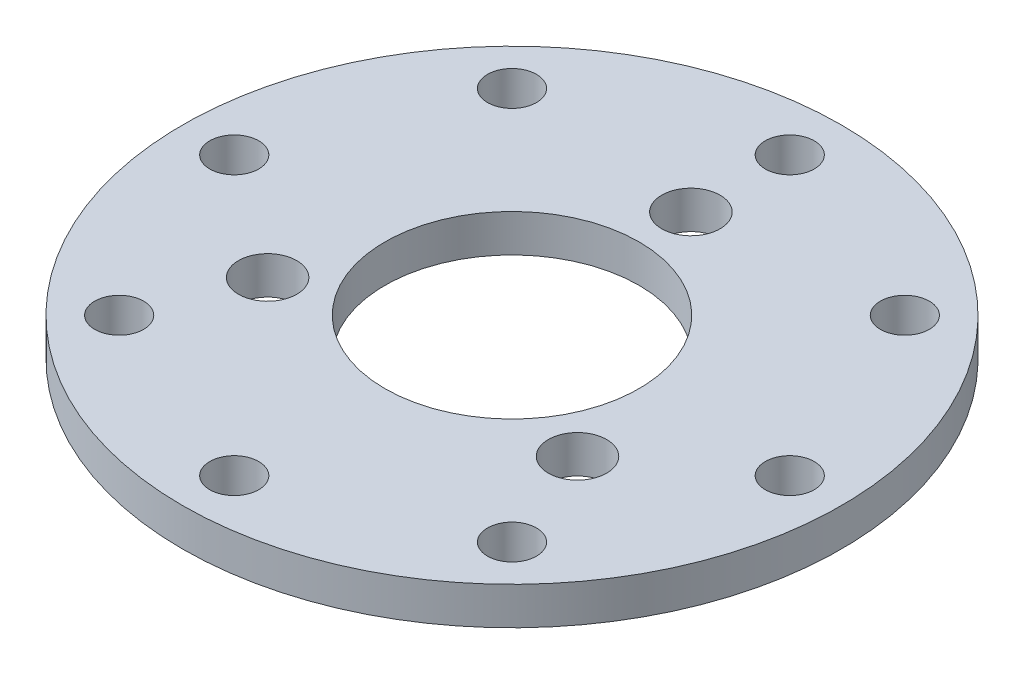
SolidWorks part; units mm, degrees
ref_plane "前视基准面" through (0, 0, 0) normal (0, 0, 1) x (1, 0, 0)
ref_plane "上视基准面" through (0, 0, 0) normal (0, 1, 0) x (1, 0, 0)
ref_plane "右视基准面" through (0, 0, 0) normal (1, 0, 0) x (0, 0, -1)
sketch "草图1" plane through (0, 0, 0) normal (0, 1, 0) x (1, 0, 0)
  line L0 (0, 0) -> (0, 9.5) construction
  line L1 (0, 0) -> (0, 9.5) construction
  circle A0 centre (0, 0) radius 17.5
  circle A1 centre (0, 0) radius 6.75
  circle A2 centre (0, 9.5) radius 1.55
  circle A3 centre (8.2272, -4.75) radius 1.55
  circle A4 centre (-8.2272, -4.75) radius 1.55
  dimension "D1" = 35
  dimension "D2" = 13.5
  dimension "D3" = 3.1
  dimension "D4" = 9.5
  dimension "D6" = 9.5
  dimension "D5" = 3
extrude "凸台-拉伸1" add sketch "草图1" along normal blind 2
sketch "草图2" plane through (0, 2, 0) normal (0, 1, 0) x (1, 0, 0)
  line L0 (0, 0) -> (0, 14.75) construction
  circle A0 centre (0, 14.75) radius 1.3
  dimension "D2" = 2.6
  dimension "D1" = 14.75
extrude "切除-拉伸1" cut sketch "草图2" against normal through all
pattern_circular "阵列(圆周)1" count 8 over 360 about axis through (0, 2, 0) along (0, 1, 0) of "切除-拉伸1"
